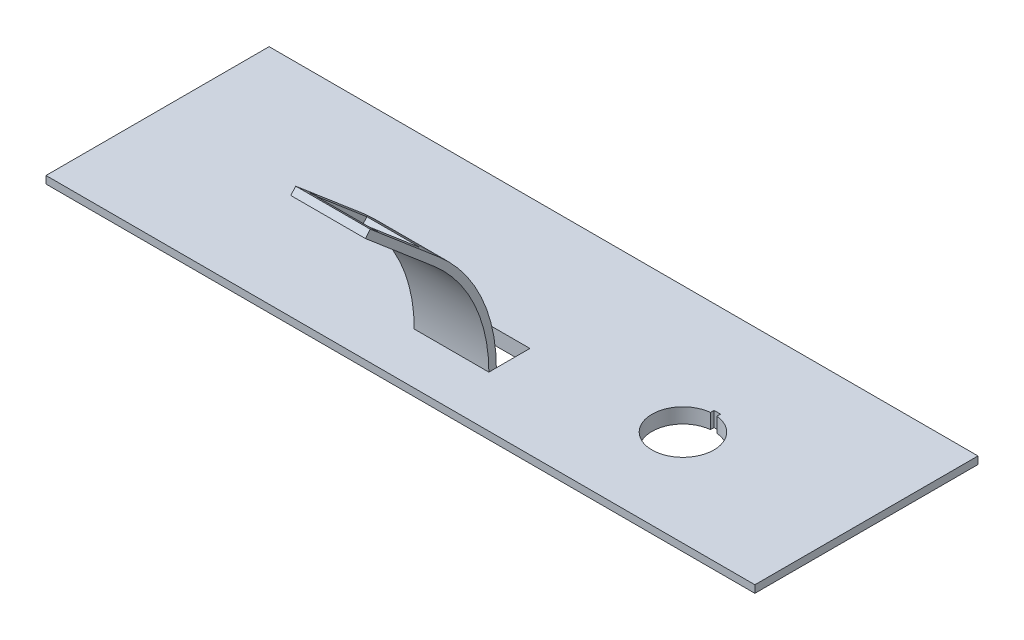
SolidWorks part; units mm, degrees
ref_plane "Front" through (0, 0, 0) normal (0, 0, 1) x (1, 0, 0)
ref_plane "Top" through (0, 0, 0) normal (0, 1, 0) x (1, 0, 0)
ref_plane "Right" through (0, 0, 0) normal (1, 0, 0) x (0, 0, -1)
sketch "Sketch1" plane through (0, 0, 0) normal (0, 1, 0) x (1, 0, 0)
  line L1 (-117.475, 34.798) -> (117.475, 34.798)
  line L2 (-117.475, 34.798) -> (-117.475, -34.798)
  line L3 (-117.475, -34.798) -> (117.475, -34.798)
  line L4 (117.475, 34.798) -> (117.475, -34.798)
  line L5 (-117.475, 34.798) -> (117.475, -34.798) construction
  line L6 (-117.475, -34.798) -> (117.475, 34.798) construction
  point P0 (0, 0)
  dimension "D1" = 69.596
  dimension "D2" = 234.95
extrude "Boss-Extrude1" add sketch "Sketch1" along normal blind 2.54
sketch "Sketch2" plane through (0, 2.54, 0) normal (0, 1, 0) x (1, 0, 0)
  line L8 (120.65, -37.973) -> (120.65, 37.973)
  line L9 (120.65, 37.973) -> (-120.65, 37.973)
  line L10 (-120.65, 37.973) -> (-120.65, -37.973)
  line L11 (-120.65, -37.973) -> (120.65, -37.973)
  line L12 (120.65, -37.973) -> (120.65, 37.973)
  line L13 (120.65, 37.973) -> (-120.65, 37.973)
  line L14 (-120.65, 37.973) -> (-120.65, -37.973)
  line L15 (-120.65, -37.973) -> (120.65, -37.973)
  dimension "D1" = 3.175
extrude "Boss-Extrude2" add sketch "Sketch2" along normal blind 2.54
sketch "Sketch3" plane through (0, 5.08, 0) normal (0, 1, 0) x (1, 0, 0)
  line L11 (-12.7, -6.604) -> (12.7, -6.604)
  line L12 (-12.7, -6.604) -> (-12.7, -18.034)
  line L13 (0, -31.2408) -> (0, 31.2408) construction
  line L15 (-12.7, -18.034) -> (12.7, -18.034)
  line L16 (12.7, -6.604) -> (12.7, -18.034)
  point P0 (0, 0)
  point P8 (0, 0)
  dimension "D6" = 11.43
extrude "Cut-Extrude2" cut sketch "Sketch3" against normal through all
sketch "Sketch4" plane through (0, 0, 0) normal (1, 0, 0) x (0, 0, -1)
  line L2 (-37.7211, 47.6552) -> (-39.3663, 45.72)
  line L4 (-37.973, 2.54) -> (37.973, 2.54)
  line L5 (37.973, 2.54) -> (37.973, 5.08)
  line L6 (37.973, 5.08) -> (-37.973, 5.08)
  line L7 (-37.973, 5.08) -> (-37.973, 2.54)
  line L9 (37.973, 2.54) -> (37.973, 5.08)
  line L11 (-37.973, 5.08) -> (-37.973, 2.54)
  line L16 (-20.574, 5.08) -> (-18.034, 5.08)
  arc A0 (-18.034, 5.08) -> (-37.7211, 47.6552) centre (-73.914, 5.08) ccw
  arc A1 (-20.574, 5.08) -> (-39.3663, 45.72) centre (-73.914, 5.08) ccw
  dimension "2" = 53.34
  dimension "D1" = 0
  dimension "D3" = 2.54
extrude "Boss-Extrude7" add sketch "Sketch4" along normal blind 12.7 and the other way blind 12.7 contours A1 A0 L2 region at (0, 28.3335, 23.6263)
sketch "Sketch5" plane through (0, 38.606, 45.4139) normal (0, 0.6477, 0.7619) x (1, 0, 0)
  line L4 (-12.7, 9.3372) -> (12.7, 9.3372)
  line L5 (12.7, 9.3372) -> (12.7, 11.8772)
  line L6 (12.7, 11.8772) -> (-12.7, 11.8772)
  line L7 (-12.7, 11.8772) -> (-12.7, 9.3372)
  line L8 (-12.7, 9.3372) -> (12.7, 9.3372)
  line L9 (12.7, 9.3372) -> (12.7, 11.8772)
  line L10 (12.7, 11.8772) -> (-12.7, 11.8772)
  line L11 (-12.7, 11.8772) -> (-12.7, 9.3372)
  dimension "D1" = 0
extrude "Boss-Extrude8" add sketch "Sketch5" along normal blind 30.48
sketch "Sketch6" plane through (0, 9.0493, -7.6927) normal (0, 0.7619, -0.6477) x (1, 0, 0)
  line L0 (0, -31.2408) -> (0, 31.2408) construction
  line L1 (-9.144, -62.9463) -> (9.144, -62.9463)
  line L2 (-9.144, -62.9463) -> (-9.144, -85.9651)
  line L3 (-9.144, -85.9651) -> (9.144, -85.9651)
  line L4 (12.7, -59.6057) -> (-12.7, -59.6057)
  line L5 (-12.7, -59.6057) -> (-12.7, -90.0857)
  line L6 (-12.7, -90.0857) -> (12.7, -90.0857)
  line L7 (12.7, -90.0857) -> (12.7, -59.6057)
  line L8 (12.7, -59.6057) -> (-12.7, -59.6057)
  line L9 (-12.7, -59.6057) -> (-12.7, -90.0857)
  line L10 (-12.7, -90.0857) -> (12.7, -90.0857)
  line L11 (12.7, -90.0857) -> (12.7, -59.6057)
  line L12 (9.144, -62.9463) -> (9.144, -85.9651)
  line L13 (-9.144, -62.9463) -> (9.144, -85.9651) construction
  line L14 (-9.144, -85.9651) -> (9.144, -62.9463) construction
  point P2 (0, -74.4557)
  dimension "D2" = 18.288
  dimension "D3" = 23.0188
  dimension "D1" = 0
extrude "Cut-Extrude3" cut sketch "Sketch6" against normal up to next contours L12 L1 L2 L3 region at (0, 57.2734, 49.0354)
sketch "Sketch9" plane through (0, 9.0493, -7.6927) normal (0, 0.7619, -0.6477) x (1, 0, 0)
  line L0 (0, -31.2408) -> (0, 31.2408) construction
  line L2 (-9.144, -62.9463) -> (9.144, -62.9463) construction
  circle A0 centre (-10.3187, -85.1713) radius 1
  circle A1 centre (10.3187, -85.1713) radius 1
  dimension "D3" = 2
  dimension "D1" = 22.225
  dimension "D2" = 20.6375
extrude "Cut-Extrude4" cut sketch "Sketch9" against normal up to next
sketch "Sketch10" plane through (0, 5.08, 0) normal (0, 1, 0) x (1, 0, 0)
  line L0 (63.4007, -5.2112) -> (63.4007, 10.0321) construction
  line L1 (62.3007, 6.4723) -> (64.5007, 6.4723)
  line L2 (64.5007, 6.4723) -> (64.5007, 5.2723)
  line L3 (62.3007, 6.4723) -> (62.3007, 5.2723)
  arc A0 (62.3007, 5.2723) -> (64.5007, 5.2723) centre (63.4007, -5.2112) ccw
  point P8 (63.4007, 6.4723)
  dimension "D1" = 21.082
  dimension "D2" = 1.1
  dimension "D3" = 1.2
extrude "Cut-Extrude6" cut sketch "Sketch10" against normal up to next
